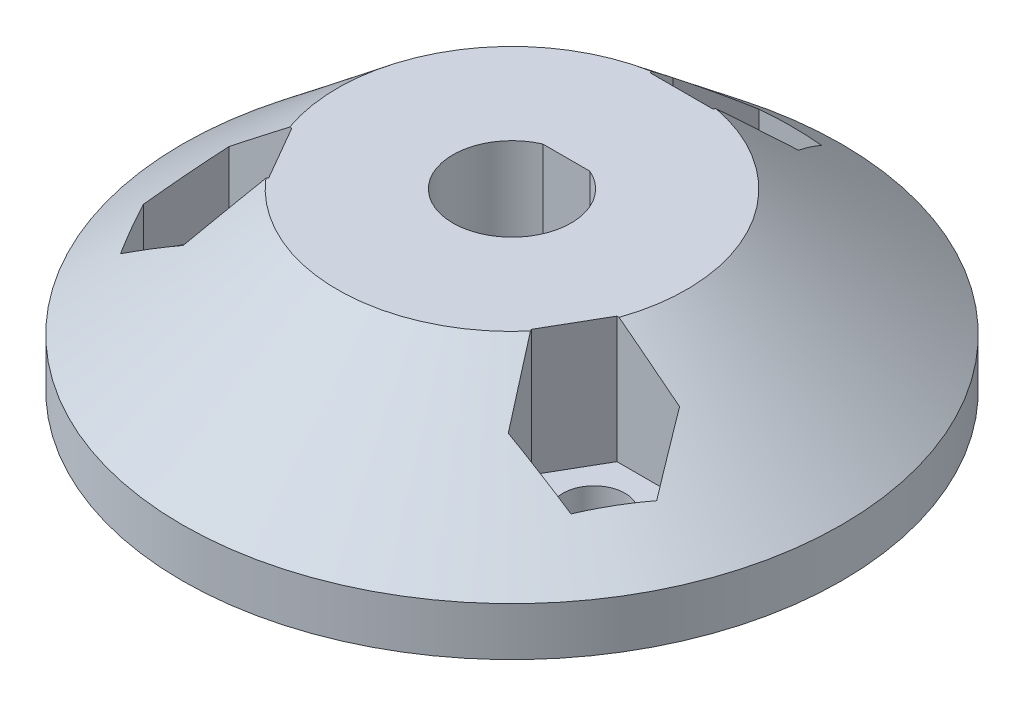
SolidWorks part; units mm, degrees
ref_plane "Plan de face" through (0, 0, 0) normal (0, 0, 1) x (1, 0, 0)
ref_plane "Plan de dessus" through (0, 0, 0) normal (0, 1, 0) x (1, 0, 0)
ref_plane "Plan de droite" through (0, 0, 0) normal (1, 0, 0) x (0, 0, -1)
sketch "Esquisse3" plane through (0, 0, 0) normal (0, 0, 1) x (1, 0, 0)
  line L0 (0, 0) -> (0, 38033.0469) construction
  line L1 (0, 0) -> (17, 0)
  line L2 (17, 0) -> (17, 2.5)
  line L3 (17, 2.5) -> (9, 9)
  line L4 (9, 9) -> (0, 9)
  line L5 (0, 9) -> (0, 0)
  line L7 (0, 0) -> (6.4, 0)
  line L8 (0, 0) -> (0, -6)
  line L9 (0, -6) -> (6.4, -6)
  line L10 (6.4, 0) -> (6.4, -6)
  dimension "D1" = 34
  dimension "D2" = 2.5
  dimension "D3" = 9
  dimension "D4" = 18
  dimension "D5" = 12.8
  dimension "D6" = 15
revolve "Révolution1" add sketch "Esquisse3" angle 360 about L0 region at (7.3058, 4.0223, 0) region at (3.2, -3, 0)
sketch "Esquisse5" plane through (0, 0, 0) normal (0, 1, 0) x (1, 0, 0)
  line L1 (10, -5.7735) -> (0, 11.547) construction
  line L2 (0, 11.547) -> (-10, -5.7735) construction
  line L3 (-10, -5.7735) -> (10, -5.7735) construction
  line L4 (1.6166, 8.747) -> (3.2332, 11.547)
  line L5 (3.2332, 11.547) -> (1.6166, 14.347)
  line L6 (1.6166, 14.347) -> (-1.6166, 14.347)
  line L7 (-1.6166, 14.347) -> (-3.2332, 11.547)
  line L8 (-3.2332, 11.547) -> (-1.6166, 8.747)
  line L9 (-1.6166, 8.747) -> (1.6166, 8.747)
  circle A0 centre (0, 0) radius 5.7735 construction
  circle A1 centre (0, 11.547) radius 1.6
  circle A2 centre (0, 11.547) radius 2.8 construction
  dimension "D2" = 3.2
  dimension "D1" = 20
  dimension "D3" = 5.6
extrude "Enlèv. mat.-Extru.1" cut sketch "Esquisse5" along normal through all from offset 2.5
extrude "Enlèv. mat.-Extru.2" cut sketch "Esquisse5<2>" against normal through all and the other way through all contours A1 region at (0, 0, -11.547)
sketch "Esquisse5<2>" plane through (0, 0, 0) normal (0, 1, 0) x (1, 0, 0) same geometry as "Esquisse5"
ref_axis "Axe1" through (0, 9.75, 0) along (0, -1, 0)
pattern_circular "Répétition circulaire1" count 3 over 360 about axis through (0, 9.75, 0) along (0, -1, 0) of "Enlèv. mat.-Extru.1", "Enlèv. mat.-Extru.2"
sketch "Esquisse6" plane through (0, 9, 0) normal (0, 1, 0) x (1, 0, 0)
  line L0 (-1.2093, 2.8) -> (1.2093, 2.8)
  circle A0 centre (0, 0) radius 3.05
  circle A1 centre (0, 0) radius 2.8 construction
  dimension "D1" = 6.1
  dimension "D2" = 5.6
extrude "Enlèv. mat.-Extru.3" cut sketch "Esquisse6" against normal through all contours L0 A0 region at (0, 9, 0.0409)
